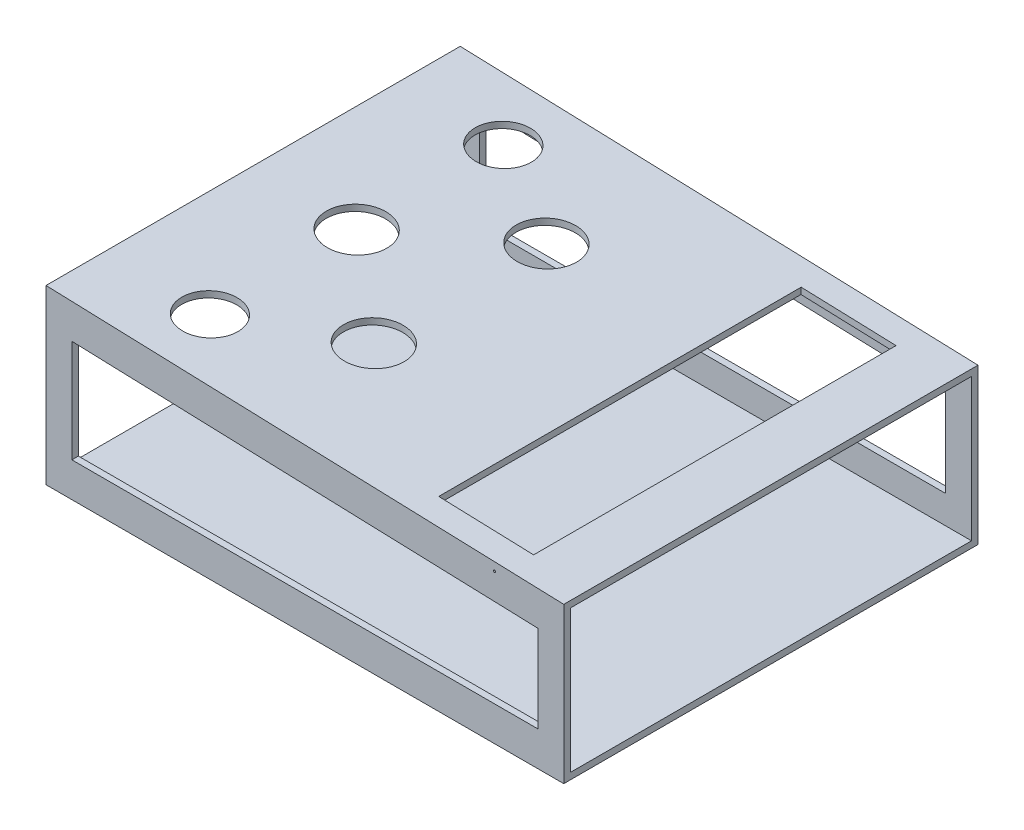
SolidWorks part; units mm, degrees
material "Balsa"
ref_plane "Front Plane" through (0, 0, 0) normal (0, 0, 1) x (1, 0, 0)
ref_plane "Top Plane" through (0, 0, 0) normal (0, 1, 0) x (1, 0, 0)
ref_plane "Right Plane" through (0, 0, 0) normal (1, 0, 0) x (0, 0, -1)
sketch "Sketch1" plane through (0, 0, 0) normal (0, 0, 1) x (1, 0, 0)
  line L0 (-373.9816, 0) -> (388.0184, 0)
  line L1 (-373.9816, 0) -> (-373.9816, 254)
  line L2 (388.0184, 0) -> (388.0184, 228.6)
  line L3 (-373.9816, 254) -> (388.0184, 228.6)
  line L4 (388.0184, 228.6) -> (-373.9816, 228.6) construction
  line L5 (-348.1349, 0) -> (-348.1349, 22.3158) construction
  line L6 (-348.1349, 22.3158) -> (-373.9816, 22.3158) construction
  point P4 (0, 0)
  point P5 (7.0184, 0)
  dimension "D1" = 762
  dimension "D2" = 254
  dimension "D3" = 228.6
extrude "Boss-Extrude1" add sketch "Sketch1" against normal blind 609.6
shell "Shell1" thickness 9.525 removed face at (-373.9816, 127, -304.8) removed face at (388.0184, 114.3, -304.8)
sketch "Sketch2" plane through (0, 0, 0) normal (0, 0, 1) x (1, 0, 0)
  line L0 (-335.8816, 201.9018) -> (349.9184, 179.0418)
  line L2 (349.9184, 179.0418) -> (349.9184, 50.8)
  line L3 (349.9184, 50.8) -> (-335.8816, 50.8)
  line L4 (-335.8816, 50.8) -> (-335.8816, 201.9018)
  line L5 (-373.9816, 0) -> (388.0184, 0) construction
  line L6 (388.0184, 0) -> (388.0184, 228.6) construction
  line L7 (388.0184, 228.6) -> (-373.9816, 254) construction
  line L8 (-373.9816, 254) -> (-373.9816, 0) construction
  point P3 (349.9184, 114.9209)
  dimension "D1" = 50.8
  dimension "D2" = 38.1
  dimension "D3" = 38.1
  dimension "D4" = 50.8
extrude "Cut-Extrude1" cut sketch "Sketch2" against normal up to surface (609.6 mm away) up to face at (7.0184, 120.65, -609.6)
sketch "Sketch5" plane through (0, 0, -600.075) normal (0, 0, 1) x (1, 0, 0)
  line L0 (-373.9816, 132.965) -> (-278.7316, 132.965) construction
  line L1 (-373.9816, 254) -> (-373.9816, 0) construction
  line L2 (-278.7316, 132.965) -> (-278.7316, 50.8) construction
  line L3 (-335.8816, 50.8) -> (349.9184, 50.8) construction
  line L4 (-278.7316, 50.8) -> (464.2184, 76.6965)
  line L5 (388.0184, 50.8) -> (464.2184, 50.8) construction
  line L6 (388.0184, 0) -> (388.0184, 228.6) construction
  line L7 (464.2184, 50.8) -> (464.2184, 76.6965) construction
  line L8 (-278.7316, 50.8) -> (-278.7316, 9.525)
  line L9 (-373.9816, 9.525) -> (388.0184, 9.525) construction
  line L10 (-278.7316, 9.525) -> (464.2184, 9.525)
  line L11 (464.2184, 9.525) -> (464.2184, 76.6965)
  dimension "D1" = 95.25
  dimension "D2" = 76.2
sketch "Sketch10" plane through (8.0422, 241.2659, 0) normal (0.0333, 0.9994, 0) x (0.9994, -0.0333, 0)
  line L0 (-229.836, 609.6) -> (-229.836, 0) construction
  line L1 (380.1873, 609.6) -> (-382.236, 609.6) construction
  line L2 (380.1873, 0) -> (-382.236, 0) construction
  line L3 (-382.236, 609.6) -> (-382.236, 0) construction
  line L4 (-382.236, 304.8) -> (380.1873, 304.8) construction
  line L5 (380.1873, 609.6) -> (380.1873, 0) construction
  line L6 (-77.436, 609.6) -> (-77.436, 0) construction
  circle A1 centre (-229.836, 88.9) radius 41.275
  circle A2 centre (-229.836, 520.7) radius 41.275
  circle A5 centre (-77.436, 431.8) radius 44.45
  circle A6 centre (-77.436, 177.8) radius 44.45
  circle A7 centre (-229.836, 304.8) radius 44.45
  dimension "D2" = 82.55
  dimension "D7" = 177.8
  dimension "D8" = 88.9
  dimension "D1" = 152.4
  dimension "D4" = 304.8
  dimension "D5" = 88.9
  dimension "D6" = 304.8
extrude "Cut-Extrude3" cut sketch "Sketch10" against normal up to surface (9.525 mm away) up to face at (7.0184, 231.7697, -304.8)
sketch "Sketch12" plane through (8.0422, 241.2659, 0) normal (0.0333, 0.9994, 0) x (0.9994, -0.0333, 0)
  line L0 (297.6373, 0) -> (297.6373, 609.6) construction
  line L1 (380.1873, 0) -> (-382.236, 0) construction
  line L2 (380.1873, 609.6) -> (-382.236, 609.6) construction
  line L3 (380.1873, 609.6) -> (380.1873, 0) construction
  line L4 (297.6373, 38.1) -> (166.1086, 38.1) construction
  line L6 (297.6373, 38.1) -> (157.9373, 38.1)
  line L7 (297.6373, 38.1) -> (297.6373, 571.5)
  line L8 (297.6373, 571.5) -> (157.9373, 571.5)
  line L9 (157.9373, 38.1) -> (157.9373, 571.5)
  dimension "D1" = 82.55
  dimension "D2" = 38.1
  dimension "D3" = 38.1
  dimension "D5" = 139.7
extrude "Cut-Extrude4" cut sketch "Sketch12" against normal up to surface (9.525 mm away) up to face at (-114.0934, 235.8068, -177.8)
sketch "Sketch13" plane through (0, 0, 0) normal (0, 0, 1) x (1, 0, 0)
  line L0 (388.0184, 228.6) -> (-373.9816, 254) construction
  circle A0 centre (301.331, 209.8876) radius 9.525
  dimension "D1" = 19.05
  dimension "D2" = 21.59
sketch "Sketch14" plane through (0, 0, -609.6) normal (0, 0, -1) x (-1, 0, 0)
  circle A0 centre (-286.0508, 219.8133) radius 1.5875
  point P2 (-286.0508, 219.8133)
extrude "Cut-Extrude5" cut sketch "Sketch14" against normal up to surface (609.6 mm away) up to face at (7.0184, 120.6359, 0)
